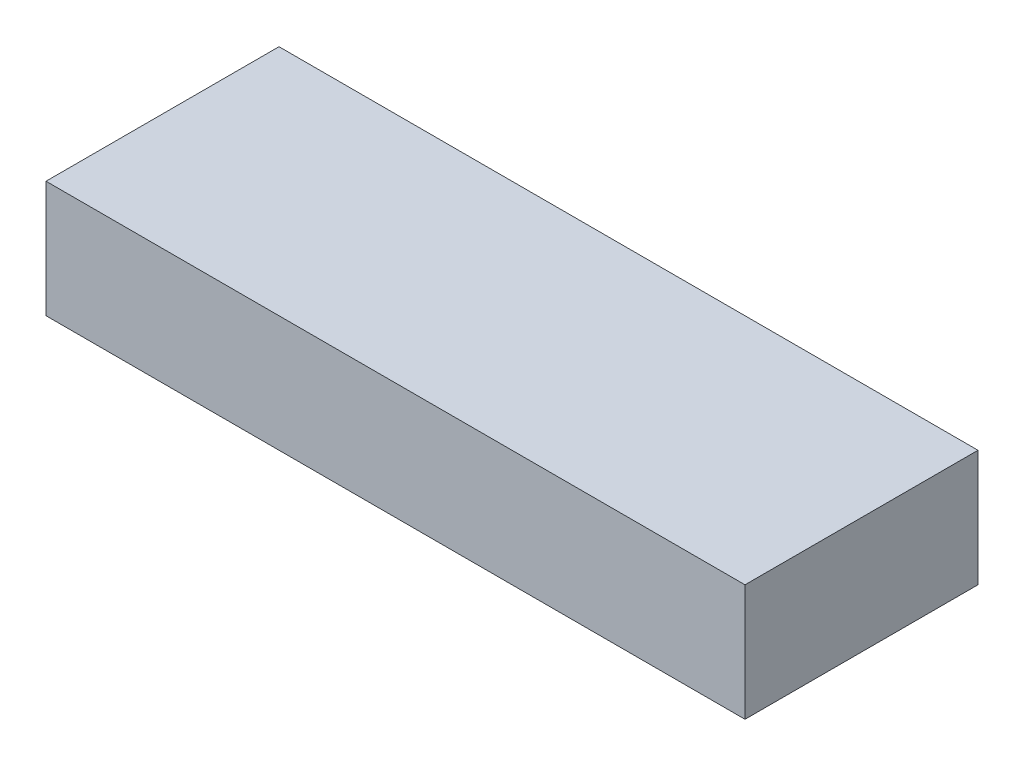
SolidWorks part; units mm, degrees
material "自定义塑料"
ref_plane "前视基准面" through (0, 0, 0) normal (0, 0, 1) x (1, 0, 0)
ref_plane "上视基准面" through (0, 0, 0) normal (0, 1, 0) x (1, 0, 0)
ref_plane "右视基准面" through (0, 0, 0) normal (1, 0, 0) x (0, 0, -1)
other "Configuration Table"
sketch "草图1" plane through (0, 0, 0) normal (0, 1, 0) x (1, 0, 0)
  line L1 (-90, -30) -> (90, -30)
  line L2 (-90, -30) -> (-90, 30)
  line L3 (-90, 30) -> (90, 30)
  line L4 (90, -30) -> (90, 30)
  line L5 (-90, -30) -> (90, 30) construction
  line L6 (-90, 30) -> (90, -30) construction
  point P0 (0, 0)
  dimension "D1" = 60
  dimension "D2" = 180
extrude "凸台-拉伸1" add sketch "草图1" along normal blind 15 and the other way blind 15
sketch "草图2" plane through (0, -15, 0) normal (0, -1, 0) x (1, 0, 0)
  line L0 (0, -30) -> (0, 30)
  line L1 (90, -30) -> (-90, -30) construction
  line L2 (-90, 30) -> (90, 30) construction
ref_axis "基准轴1" through (0, -15, -30) along (0, 0, 1)
